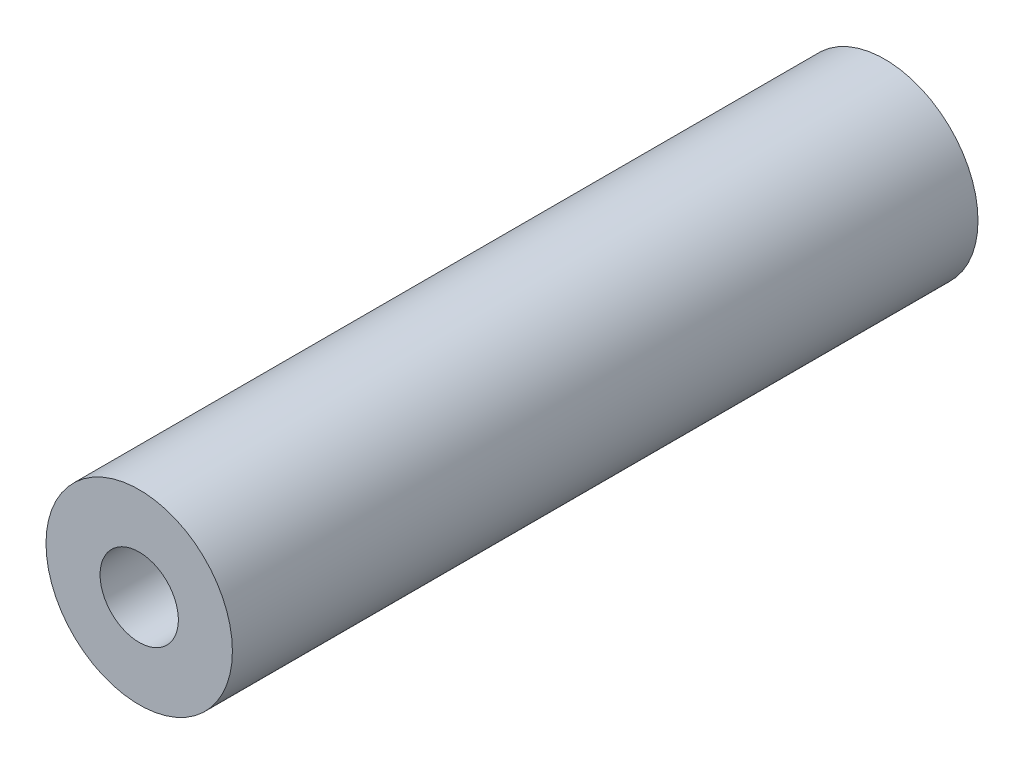
SolidWorks part; units mm, degrees
ref_plane "Front Plane" through (0, 0, 0) normal (0, 0, 1) x (1, 0, 0)
ref_plane "Top Plane" through (0, 0, 0) normal (0, 1, 0) x (1, 0, 0)
ref_plane "Right Plane" through (0, 0, 0) normal (1, 0, 0) x (0, 0, -1)
sketch "Sketch1" plane through (0, 0, 0) normal (0, 0, 1) x (1, 0, 0)
  circle A0 centre (0, 0) radius 9.525
  circle A1 centre (0, 0) radius 4.0005
  dimension "OD" = 19.05
  dimension "ID" = 8.001
extrude "Extrude1" add sketch "Sketch1" along normal mid plane 76.2
sketch "Sketch2" plane through (0, 0, 0) normal (1, 0, 0) x (0, 0, -1)
  line L0 (-38.1, -4.0005) -> (38.1, -4.0005) construction
  line L3 (38.1, 4.0005) -> (-38.1, 4.0005) construction
  line L5 (-38.1, -4.0005) -> (38.1, -4.0005)
  line L6 (38.1, 4.0005) -> (-38.1, 4.0005)
sketch "Sketch4" plane through (0, 0, 38.1) normal (0, 0, 1) x (1, 0, 0)
  line L0 (0, 0) -> (-2.8288, 2.8288)
  line L1 (0, -10.4775) -> (0, 10.4775) construction
  circle A0 centre (0, 0) radius 4.0005 construction
  dimension "D1" = 45
